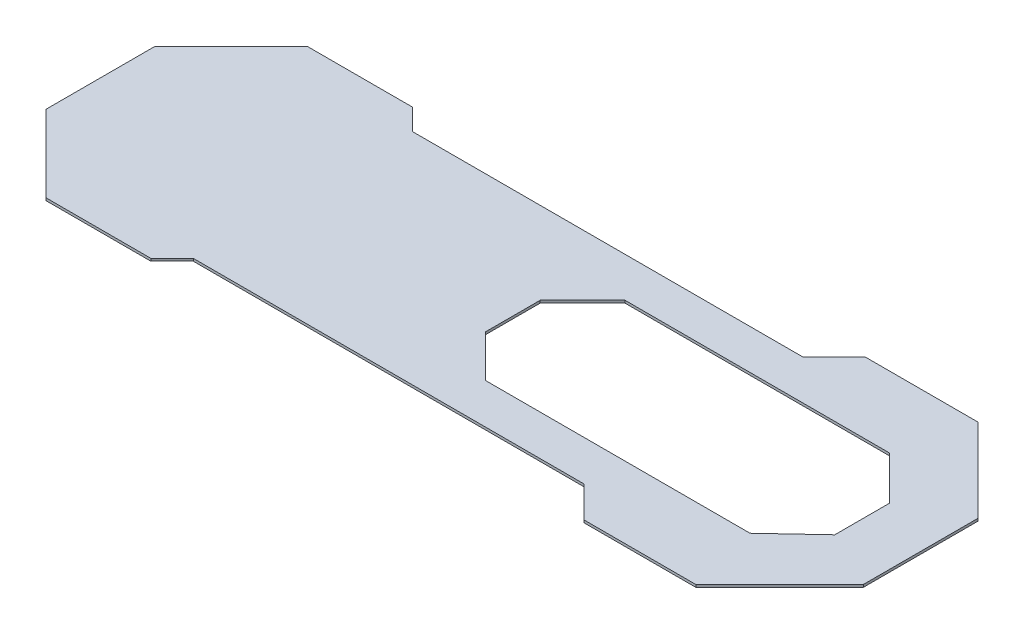
SolidWorks part; units mm, degrees
ref_plane "Спереди" through (0, 0, 0) normal (0, 0, 1) x (1, 0, 0)
ref_plane "Сверху" through (0, 0, 0) normal (0, 1, 0) x (1, 0, 0)
ref_plane "Справа" through (0, 0, 0) normal (1, 0, 0) x (0, 0, -1)
sketch "Эскиз1" plane through (0, 0, 0) normal (0, 1, 0) x (1, 0, 0)
  line L0 (-57.721, -161.8896) -> (-213.1575, -161.8896)
  line L1 (-57.721, -161.8896) -> (-57.0996, -161.8896)
  line L2 (-222.2788, -153.3896) -> (-214.2181, -161.4503)
  line L3 (-56.6603, -161.4503) -> (-57.0996, -161.8896)
  line L4 (-44.5996, -149.3896) -> (-56.6603, -161.4503)
  line L5 (-56.6603, -250.329) -> (-57.0996, -249.8896)
  line L6 (0.4781, -149.3896) -> (-44.5996, -149.3896)
  line L7 (-57.721, -249.8896) -> (-57.0996, -249.8896)
  line L8 (33.8892, -182.8008) -> (0.4781, -149.3896)
  line L9 (-213.1575, -161.8896) -> (-213.7788, -161.8896)
  line L10 (33.8892, -228.7785) -> (33.8892, -182.8008)
  line L11 (-214.2181, -161.4503) -> (-213.7788, -161.8896)
  line L12 (33.8892, -228.7785) -> (0.2781, -262.3896)
  line L13 (-214.2181, -250.329) -> (-213.7788, -249.8896)
  line L14 (-44.5996, -262.3896) -> (0.2781, -262.3896)
  line L15 (-213.1575, -249.8896) -> (-213.7788, -249.8896)
  line L16 (-56.6603, -250.329) -> (-44.5996, -262.3896)
  line L18 (-213.1575, -249.8896) -> (-57.721, -249.8896)
  line L20 (-222.2788, -258.3896) -> (-214.2181, -250.329)
  line L22 (-264.357, -258.3896) -> (-222.2788, -258.3896)
  line L24 (-295.1108, -227.6359) -> (-264.357, -258.3896)
  line L26 (-264.357, -153.3896) -> (-222.2788, -153.3896)
  line L28 (-295.1108, -184.1434) -> (-264.357, -153.3896)
  line L30 (-295.1108, -184.1434) -> (-295.1108, -227.6359)
  dimension "D1" = 135
  dimension "D2" = 225
  dimension "D3" = 225
  dimension "D4" = 225
  dimension "D5" = 135
  dimension "D6" = 225
  dimension "D7" = 225
  dimension "D8" = 225
  dimension "D9" = 135
  dimension "D10" = 135
  dimension "D11" = 135
  dimension "D12" = 135
  dimension "D13" = 135
  dimension "D14" = 135
  dimension "D15" = 45.0777
  dimension "D16" = 135
  dimension "D17" = 135
  dimension "D18" = 135
sheet metal parameters "Листовой металл1" thickness 1 parameters "D1"=1.2, "Толщина"=1
sheet metal parameters "Листовой металл2" thickness 1 parameters "D1"=1.2, "Толщина"=1
base flange "Базовая кромка1" sketch "Эскиз1" thickness 1 reverse thickness direction no parameters "D1"=1.2
sketch "Эскиз3" plane through (0, 0, 0) normal (0, 1, 0) x (1, 0, 0)
  line L0 (-129.6506, -194.8548) -> (-112.6623, -177.8665)
  line L1 (-112.6623, -177.8665) -> (-6.6329, -177.8665)
  line L2 (-6.6329, -177.8665) -> (10.8952, -195.3946)
  line L3 (10.8952, -195.3946) -> (10.8952, -217.2652)
  line L4 (10.8952, -217.2652) -> (-6.6334, -233.7128)
  line L5 (-6.6334, -233.7128) -> (-112.6624, -233.7128)
  line L6 (-112.6624, -233.7128) -> (-129.6506, -216.7245)
  line L7 (-129.6506, -216.7245) -> (-129.6506, -194.8548)
  line L18 (-129.6506, -205.7896) -> (10.8952, -205.7896) construction
  line L21 (10.8952, -205.7896) -> (33.8892, -205.7896) construction
  line L22 (33.8892, -228.7785) -> (33.8892, -182.8008) construction
  dimension "D2" = 10.9349
  dimension "D3" = 10.9349
  dimension "D4" = 225
  dimension "D5" = 135
  dimension "D6" = 225
  dimension "D7" = 135
  dimension "D8" = 10.395
  dimension "D9" = 106.0294
  dimension "D10" = 24.0251
  dimension "D11" = 21.8697
  dimension "D12" = 24.025
  dimension "D13" = 106.029
  dimension "D14" = 135
extrude "Вырез-Вытянуть1" cut sketch "Эскиз3" against normal blind 10 normal cut yes
flat pattern "Развертка1" [suppressed]
sketch "Сгиб-Линии1" plane through (0, 0, 0) normal (0, 1, 0) x (1, 0, 0)
sketch3d "Граничная рамка1" [suppressed]
  line L0 (116.8178, 58.9403, 0) -> (-182.6875, 195.0932, 0) construction
  line L1 (70.054, -43.9293, 0) -> (-229.4513, 92.2236, 0) construction
  line L2 (116.8178, 58.9403, 0) -> (70.054, -43.9293, 0) construction
  line L3 (-182.6875, 195.0932, 0) -> (-229.4513, 92.2236, 0) construction
flat pattern "Развертка2" [suppressed]
sketch "Сгиб-Линии2" plane through (0, 0, 0) normal (0, 1, 0) x (1, 0, 0)
sketch "Граничная рамка2" [suppressed] plane through (0, 0, 0) normal (0, 1, 0) x (1, 0, 0)
